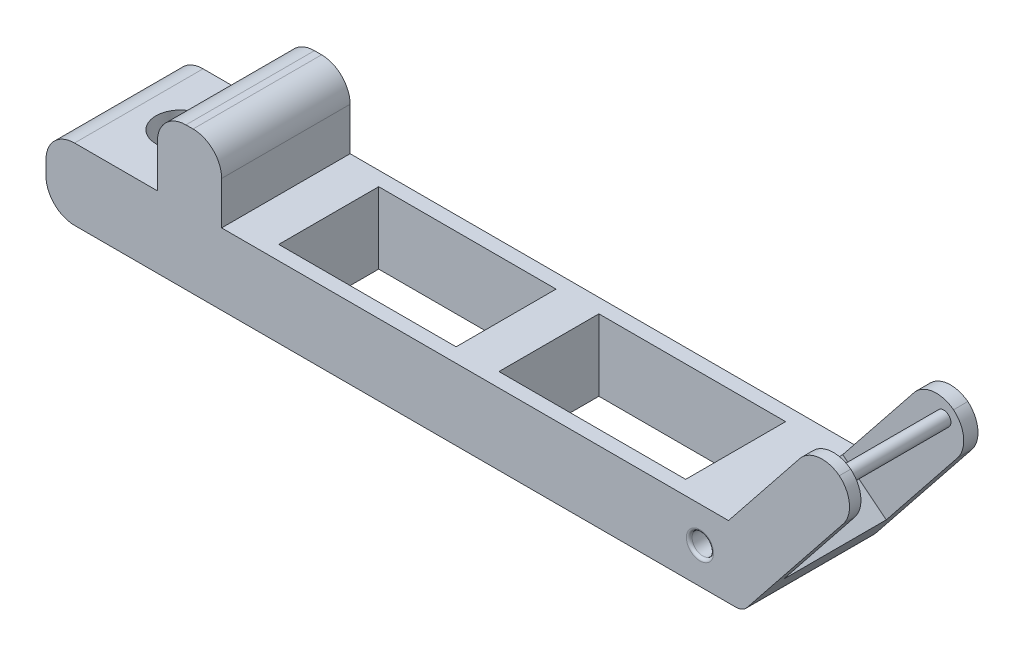
SolidWorks part; units mm, degrees
ref_plane "Front Plane" through (0, 0, 0) normal (0, 0, 1) x (1, 0, 0)
ref_plane "Top Plane" through (0, 0, 0) normal (0, 1, 0) x (1, 0, 0)
ref_plane "Right Plane" through (0, 0, 0) normal (1, 0, 0) x (0, 0, -1)
sketch "Szkic1" plane through (0, 0, 0) normal (0, 0, 1) x (1, 0, 0)
  line L6 (-27646.5587, -28.9023) -> (-27646.5587, -33.9023)
  line L7 (-27646.5587, -33.9023) -> (-27597.7587, -33.9023)
  line L8 (-27597.7587, -33.9023) -> (-27589.4735, -23.5176)
  line L9 (-27589.4735, -23.5176) -> (-27592.5221, -21.0854)
  line L10 (-27592.5221, -21.0854) -> (-27598.7587, -28.9023)
  line L11 (-27598.7587, -28.9023) -> (-27634.2587, -28.9023)
  line L12 (-27638.7587, -28.9023) -> (-27638.7587, -23.9023)
  line L13 (-27638.7587, -23.9023) -> (-27634.2587, -23.9023)
  line L14 (-27634.2587, -23.9023) -> (-27634.2587, -28.9023)
  line L15 (-27638.7587, -28.9023) -> (-27646.5587, -28.9023)
  line L16 (-27600.7587, -28.9023) -> (-27600.7587, -33.9023) construction
  circle A0 centre (-27600.7587, -31.4023) radius 0.75
  point P12 (-27600.7587, -31.4023)
  dimension "D9" = 1.5
  dimension "D1" = 3.9
  dimension "D2" = 47.8
  dimension "D3" = 10
  dimension "D4" = 5
  dimension "D5" = 48.8
  dimension "D6" = 4.5
  dimension "D7" = 5
  dimension "D8" = 7.8
  dimension "D10" = 2
extrude "Dodanie-wyciągnięcie1" add sketch "Szkic1" along normal blind 9
fillet "Zaokrąglenie1" radius 2 4 edges at (-27646.5587, -33.9023, 4.5) (-27634.2587, -23.9023, 4.5) (-27638.7587, -23.9023, 4.5) (-27646.5587, -28.9023, 4.5)
fillet "Zaokrąglenie3" radius 1 1 edges at (-27597.7587, -33.9023, 4.5)
ref_plane "Płaszczyzna1" through (0, -28.9023, 0) normal (0, 1, 0) x (1, 0, 0)
sketch "Szkic2" plane through (0, -28.9023, 0) normal (0, 1, 0) x (1, 0, 0)
  line L0 (-27641.6587, 0) -> (-27641.6587, -9) construction
  line L1 (-27638.7587, 0) -> (-27644.5587, 0) construction
  line L2 (-27638.7587, -9) -> (-27644.5587, -9) construction
  circle A0 centre (-27641.6587, -4.5) radius 1.7
  point P6 (-27641.6587, -4.5)
  dimension "D1" = 3.4
extrude "Wytnij-wyciągnięcie1" cut sketch "Szkic2" against normal through all
ref_plane "Płaszczyzna2" through (0, -28.9023, 0) normal (0, 1, 0) x (1, 0, 0)
sketch "Szkic3" plane through (0, -28.9023, 0) normal (0, 1, 0) x (1, 0, 0)
  line L0 (-27634.2587, -4.5) -> (-27598.7587, -4.5) construction
  line L1 (-27634.2587, -9) -> (-27634.2587, 0) construction
  line L2 (-27598.7587, -9) -> (-27598.7587, 0) construction
  line L3 (-27598.7587, -9) -> (-27634.2587, -9) construction
  line L4 (-27602.7587, -8) -> (-27615.8361, -8)
  line L5 (-27602.7587, -8) -> (-27602.7587, -1)
  line L6 (-27602.7587, -1) -> (-27615.8361, -1)
  line L7 (-27615.8361, -8) -> (-27615.8361, -1)
  line L8 (-27602.7587, -8) -> (-27615.8361, -1) construction
  line L9 (-27602.7587, -1) -> (-27615.8361, -8) construction
  line L10 (-27631.2587, -1) -> (-27618.8361, -1)
  line L11 (-27631.2587, -1) -> (-27631.2587, -8)
  line L12 (-27631.2587, -8) -> (-27618.8361, -8)
  line L13 (-27618.8361, -1) -> (-27618.8361, -8)
  line L14 (-27631.2587, -1) -> (-27618.8361, -8) construction
  line L15 (-27631.2587, -8) -> (-27618.8361, -1) construction
  point P6 (-27609.2974, -4.5)
  point P11 (-27625.0474, -4.5)
  dimension "D1" = 3
  dimension "D2" = 4
  dimension "D3" = 3
  dimension "D4" = 1
extrude "Wytnij-wyciągnięcie2" cut sketch "Szkic3" against normal through all
ref_plane "Płaszczyzna3" through (-16850.0467, 13443.5022, 0) normal (-0.7817, 0.6237, 0) x (0, 0, 1)
sketch "Szkic4" plane through (-16850.0467, 13443.5022, 0) normal (-0.7817, 0.6237, 0) x (0, 0, 1)
  line L0 (9, -17234.8628) -> (0, -17234.8628) construction
  line L1 (1, -17234.8628) -> (8.2, -17234.8628)
  line L2 (1, -17234.8628) -> (1, -17222.0924)
  line L3 (1, -17222.0924) -> (8.2, -17222.0924)
  line L4 (8.2, -17234.8628) -> (8.2, -17222.0924)
  line L5 (0, -17224.8628) -> (0, -17234.8628) construction
  dimension "D1" = 7.2
  dimension "D2" = 1
extrude "Wytnij-wyciągnięcie3" cut sketch "Szkic4" against normal through all
ref_plane "Płaszczyzna4" through (0, 0, 1) normal (0, 0, 1) x (1, 0, 0)
sketch "Szkic5" plane through (0, 0, 1) normal (0, 0, 1) x (1, 0, 0)
  line L0 (-27590.9978, -22.3015) -> (-27597.2344, -30.1185) construction
  line L1 (-27592.5221, -21.0854) -> (-27589.4735, -23.5176) construction
  line L2 (-27595.7101, -31.3346) -> (-27598.7587, -28.9023) construction
  circle A0 centre (-27592.3166, -23.9544) radius 0.5
  dimension "D1" = 1
extrude "Dodanie-wyciągnięcie2" [suppressed] add sketch "Szkic5" along normal up to next
fillet "Zaokrąglenie4" radius 2 4 edges at (-27589.4735, -23.5176, 0.5) (-27592.5221, -21.0854, 0.5) (-27589.4735, -23.5176, 8.6) (-27592.5221, -21.0854, 8.6)
fillet "Zaokrąglenie5" radius 1 1 edges at (-27643.3587, -33.9023, 4.5)
ref_axis "Oś1" through (-27641.6587, -32.9023, 4.5) along (0, 1, 0)
ref_point "Punkt1"
ref_point "Punkt2"
fillet "Zaokrąglenie7" radius 0.2 2 edges at (-27600.0087, -31.4023, 9) (-27600.0087, -31.4023, 0)
ref_plane "Płaszczyzna Dolnia" through (0, -33.9023, 0) normal (0, -1, 0) x (-1, 0, 0)
sketch "Szkic6" plane through (0, 0, 1) normal (0, 0, 1) x (1, 0, 0)
  line L0 (-27595.4545, -24.7608) -> (-27592.4059, -27.1931)
  line L1 (-27590.7208, -25.081) -> (-27595.7101, -31.3346) construction
  line L2 (-16849.7037, 13443.9321) -> (-16850.3897, 13443.0723) construction
  line L3 (-27593.9302, -25.977) -> (-27590.9982, -22.302)
  circle A0 centre (-27591.6842, -23.1619) radius 0.5
  arc A1 (-27590.7208, -25.081) -> (-27590.9982, -22.302) centre (-27592.2842, -23.8337) ccw construction
  point P10 (-27590.9982, -22.302)
  dimension "D1" = 1
  dimension "D2" = 1.1
extrude "Dodanie-wyciągnięcie3" add sketch "Szkic6" along normal up to surface (7.2 mm away) contours L3 A0 | L3 A0 region at (-27591.8501, -23.0295, 1) region at (-27591.5184, -23.2942, 1) up to face at (-27593.8925, -25.9297, 8.2)
